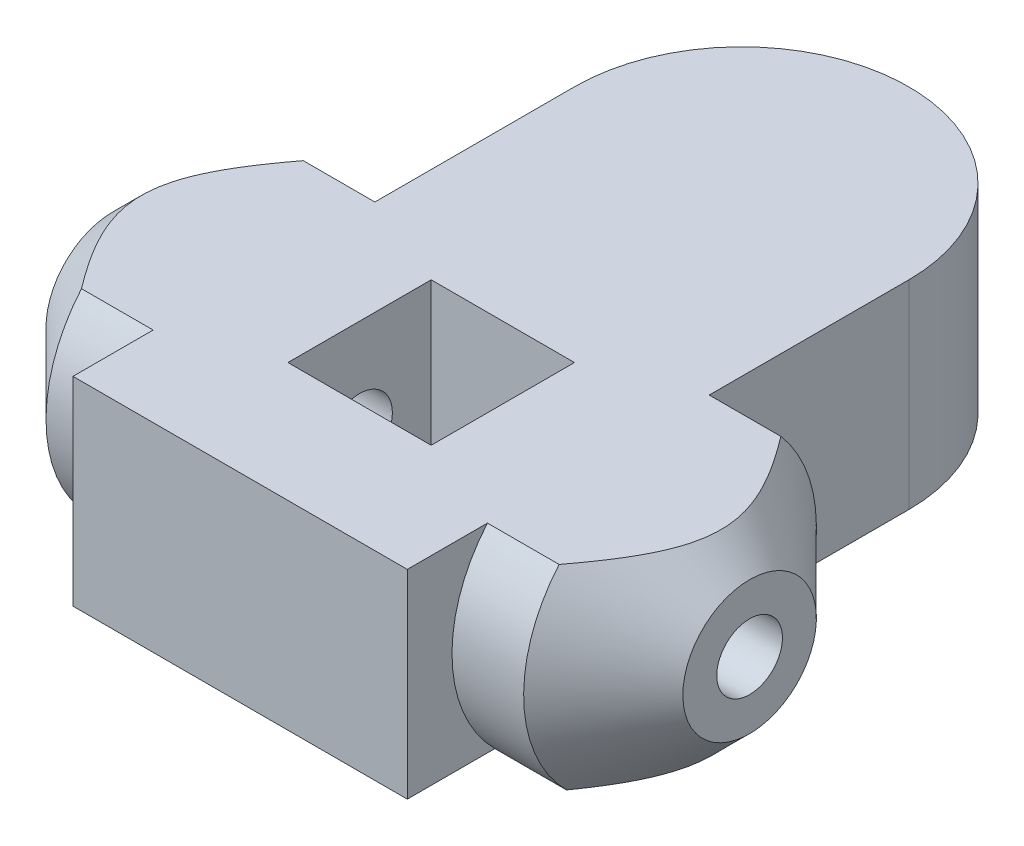
SolidWorks part; units mm, degrees
ref_plane "Front Plane" through (0, 0, 0) normal (0, 0, 1) x (1, 0, 0)
ref_plane "Top Plane" through (0, 0, 0) normal (0, 1, 0) x (1, 0, 0)
ref_plane "Right Plane" through (0, 0, 0) normal (1, 0, 0) x (0, 0, -1)
sketch "Sketch1" plane through (0, 0, 0) normal (0, 1, 0) x (1, 0, 0)
  line L0 (0, 0) -> (0, -24) construction
  line L1 (-21, -24) -> (21, -24)
  line L2 (21, -24) -> (21, 39)
  line L3 (-21, -24) -> (-21, 39)
  arc A0 (21, 39) -> (-21, 39) centre (0, 39) ccw
  dimension "D1" = 24
  dimension "D2" = 21
extrude "Boss-Extrude1" add sketch "Sketch1" along normal blind 12 and the other way blind 13
sketch "Sketch4" plane through (0, 0, 0) normal (1, 0, 0) x (0, 0, -1)
  line L0 (0, 0) -> (13, -13) construction
  line L1 (-24, -13) -> (39, -13) construction
  line L2 (13, -13) -> (-13, -13)
  line L3 (13.9284, 12) -> (-13.9284, 12)
  line L4 (-24, 12) -> (39, 12) construction
  circle A0 centre (0, 0) radius 18.3848
extrude "Boss-Extrude2" add sketch "Sketch4" along normal mid plane 80 contours L3 A0 L2 region at (0, -0.3999, 0)
sketch "Sketch2" plane through (0, 12, 0) normal (0, 1, 0) x (1, 0, 0)
  line L1 (-9, 9) -> (9, 9)
  line L2 (-9, 9) -> (-9, -9)
  line L3 (-9, -9) -> (9, -9)
  line L4 (9, 9) -> (9, -9)
  line L5 (-9, 9) -> (9, -9) construction
  line L6 (-9, -9) -> (9, 9) construction
  point P0 (0, 0)
  dimension "D1" = 18
extrude "Cut-Extrude1" cut sketch "Sketch2" against normal blind 20
sketch "Sketch5" plane through (0, 0, 0) normal (1, 0, 0) x (0, 0, -1)
  circle A0 centre (0, 0) radius 4.125
  dimension "D1" = 8.25
extrude "Cut-Extrude2" cut sketch "Sketch5" against normal through all both and the other way through all
chamfer "Chamfer1" distance 10 angle 45 2 edges at (40, -0.6823, -18.3721) (-40, -0.6823, -18.3721)
